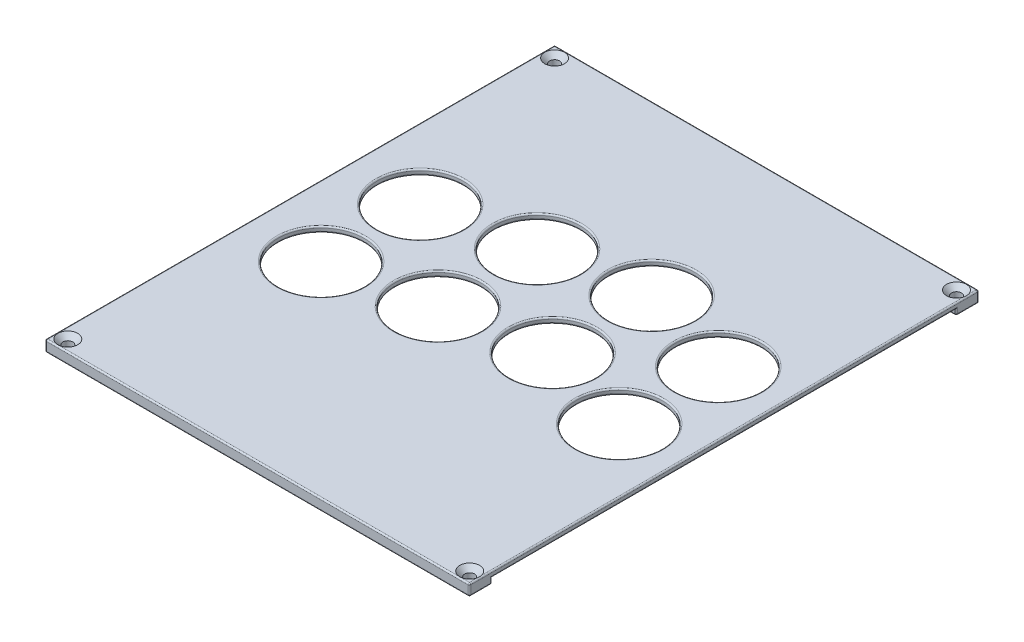
SolidWorks part; units mm, degrees
ref_plane "Front Plane" through (0, 0, 0) normal (0, 0, 1) x (1, 0, 0)
ref_plane "Top Plane" through (0, 0, 0) normal (0, 1, 0) x (1, 0, 0)
ref_plane "Right Plane" through (0, 0, 0) normal (1, 0, 0) x (0, 0, -1)
sketch "Sketch1" plane through (0, 0, 0) normal (0, 1, 0) x (1, 0, 0)
  line L0 (-125, -72.5) -> (-90.7071, -65.5) construction
  line L1 (0, 0) -> (-150, 0)
  line L2 (0, 0) -> (0, -180)
  line L3 (0, -180) -> (-150, -180)
  line L4 (-150, 0) -> (-150, -180)
  line L5 (-90.7071, -65.5) -> (-56.2253, -59.5) construction
  line L6 (-56.2253, -59.5) -> (-22.6842, -69.5) construction
  line L7 (-22.6842, -69.5) -> (-22.6842, -104.5) construction
  line L8 (-22.6842, -104.5) -> (-56.2253, -94.5) construction
  line L9 (-56.2253, -94.5) -> (-90.7071, -100.5) construction
  line L10 (-90.7071, -100.5) -> (-125, -107.5) construction
  line L11 (-125, -107.5) -> (-125, -72.5) construction
  line L12 (-90.7071, -100.5) -> (-90.7071, -65.5) construction
  line L13 (-56.2253, -94.5) -> (-56.2253, -59.5) construction
  line L14 (-22.6842, -69.5) -> (-22.6842, -59.5) construction
  line L15 (-22.6842, -59.5) -> (-56.2253, -59.5) construction
  line L16 (-56.2253, -59.5) -> (-90.7071, -59.5) construction
  line L17 (-90.7071, -65.5) -> (-90.7071, -59.5) construction
  line L18 (-90.7071, -65.5) -> (-125, -65.5) construction
  line L19 (-125, -65.5) -> (-125, -72.5) construction
  line L20 (-125, -72.5) -> (-150, -72.5) construction
  line L21 (-125, -72.5) -> (-125, 0) construction
  line L22 (-22.6842, -69.5) -> (0, -69.5) construction
  line L23 (-75, -145) -> (-150, -145) construction
  line L24 (-150, -172) -> (-142, -172) construction
  line L25 (-142, -172) -> (-142, -180) construction
  line L26 (-8, -180) -> (-8, -172) construction
  line L27 (-8, -172) -> (0, -172) construction
  line L28 (0, -8) -> (-8, -8) construction
  line L29 (-8, -8) -> (-8, 0) construction
  line L30 (-142, 0) -> (-142, -8) construction
  line L31 (-142, -8) -> (-150, -8) construction
  line L32 (-142, -8) -> (-150, 0) construction
  line L33 (-8, -8) -> (0, 0) construction
  line L34 (-8, -172) -> (0, -180) construction
  line L35 (-150, -180) -> (-142, -172) construction
  line L36 (-125, -107.5) -> (-125, -180) construction
  line L37 (-47.5, -162) -> (-102.5, -162) construction
  line L38 (-47.5, -162) -> (-47.5, -128) construction
  line L39 (-47.5, -128) -> (-102.5, -128) construction
  line L40 (-102.5, -162) -> (-102.5, -128) construction
  line L41 (-47.5, -162) -> (-102.5, -128) construction
  line L42 (-47.5, -128) -> (-102.5, -162) construction
  line L43 (-75, -145) -> (0, -145) construction
  line L44 (-75, -145) -> (-75, -180) construction
  line L45 (-142, -2) -> (-8, -2)
  line L46 (-100.1329, -128) -> (-101.3164, -125.95)
  line L47 (-101.3164, -125.95) -> (-103.6836, -125.95)
  line L48 (-103.6836, -125.95) -> (-104.8671, -128)
  line L49 (-104.8671, -128) -> (-103.6836, -130.05)
  line L50 (-103.6836, -130.05) -> (-101.3164, -130.05)
  line L51 (-101.3164, -130.05) -> (-100.1329, -128)
  line L52 (-45.1329, -128) -> (-46.3164, -125.95)
  line L53 (-46.3164, -125.95) -> (-48.6836, -125.95)
  line L54 (-48.6836, -125.95) -> (-49.8671, -128)
  line L55 (-49.8671, -128) -> (-48.6836, -130.05)
  line L56 (-48.6836, -130.05) -> (-46.3164, -130.05)
  line L57 (-46.3164, -130.05) -> (-45.1329, -128)
  line L58 (-46.3164, -164.05) -> (-45.1329, -162)
  line L59 (-45.1329, -162) -> (-46.3164, -159.95)
  line L60 (-46.3164, -159.95) -> (-48.6836, -159.95)
  line L61 (-48.6836, -159.95) -> (-49.8671, -162)
  line L62 (-49.8671, -162) -> (-48.6836, -164.05)
  line L63 (-48.6836, -164.05) -> (-46.3164, -164.05)
  line L64 (-100.1329, -162) -> (-101.3164, -159.95)
  line L65 (-101.3164, -159.95) -> (-103.6836, -159.95)
  line L66 (-103.6836, -159.95) -> (-104.8671, -162)
  line L67 (-104.8671, -162) -> (-103.6836, -164.05)
  line L68 (-103.6836, -164.05) -> (-101.3164, -164.05)
  line L69 (-101.3164, -164.05) -> (-100.1329, -162)
  line L70 (-106, -166) -> (-44, -166)
  line L71 (-106, -166) -> (-106, -124)
  line L72 (-106, -124) -> (-44, -124)
  line L73 (-44, -166) -> (-44, -124)
  line L74 (-106, -166) -> (-44, -124) construction
  line L75 (-106, -124) -> (-44, -166) construction
  line L76 (-148, -8) -> (-148, -172)
  line L77 (-142, -178) -> (-8, -178)
  line L78 (-142, -2) -> (-142, -8)
  line L79 (-142, -8) -> (-148, -8)
  line L80 (-8, -2) -> (-8, -8)
  line L81 (-8, -8) -> (0, -8)
  line L82 (0, -172) -> (-8, -172)
  line L83 (-8, -172) -> (-8, -178)
  line L84 (-142, -178) -> (-142, -172)
  line L85 (-142, -172) -> (-148, -172)
  line L86 (-145.7, -90) -> (-145.7, -80)
  line L87 (-2.3, -2.3) -> (-147.7, -2.3) construction
  line L89 (-2.3, -177.7) -> (-147.7, -177.7) construction
  line L90 (-2.3, -2.3) -> (-2.3, -177.7) construction
  line L91 (-75, -2.3) -> (-65, -2.3)
  line L92 (-65, -2.3) -> (-65, -4.3)
  line L93 (-65, -4.3) -> (-85, -4.3)
  line L94 (-85, -4.3) -> (-85, -2.3)
  line L95 (-85, -2.3) -> (-75, -2.3)
  line L96 (-145.7, -80) -> (-143.7, -80)
  line L97 (-143.7, -80) -> (-143.7, -100)
  line L98 (-143.7, -100) -> (-145.7, -100)
  line L99 (-145.7, -100) -> (-145.7, -90)
  line L100 (-75, -177.7) -> (-65, -177.7)
  line L101 (-65, -177.7) -> (-65, -175.7)
  line L102 (-65, -175.7) -> (-85, -175.7)
  line L103 (-85, -175.7) -> (-85, -177.7)
  line L104 (-85, -177.7) -> (-75, -177.7)
  line L105 (-147.7, -2.3) -> (-147.7, -177.7) construction
  line L106 (-148, -90) -> (-145.7, -90) construction
  circle A16 centre (-125, -72.5) radius 15 construction
  circle A17 centre (-90.7071, -65.5) radius 15 construction
  circle A18 centre (-56.2253, -59.5) radius 15 construction
  circle A19 centre (-22.6842, -69.5) radius 15 construction
  circle A20 centre (-125, -107.5) radius 15 construction
  circle A21 centre (-90.7071, -100.5) radius 15 construction
  circle A22 centre (-56.2253, -94.5) radius 15 construction
  circle A23 centre (-22.6842, -104.5) radius 15 construction
  circle A24 centre (-125, -72.5) radius 15.2
  circle A25 centre (-90.7071, -65.5) radius 15.2
  circle A26 centre (-56.2253, -59.5) radius 15.2
  circle A27 centre (-22.6842, -69.5) radius 15.2
  circle A28 centre (-22.6842, -104.5) radius 15.2
  circle A29 centre (-56.2253, -94.5) radius 15.2
  circle A30 centre (-90.7071, -100.5) radius 15.2
  circle A31 centre (-125, -107.5) radius 15.2
  circle A32 centre (-146, -4) radius 1.75
  circle A33 centre (-4, -4) radius 1.75
  circle A34 centre (-4, -176) radius 1.75
  circle A35 centre (-146, -176) radius 1.75
  circle A36 centre (-102.5, -128) radius 2.05 construction
  circle A37 centre (-47.5, -128) radius 2.05 construction
  circle A38 centre (-47.5, -162) radius 2.05 construction
  circle A39 centre (-102.5, -162) radius 2.05 construction
  point P23 (-75, -145)
  dimension "D1" = 30
  dimension "D7" = 3.5
  dimension "D14" = 4.1
  dimension "D22" = 2.3
  dimension "D3" = 10
  dimension "D4" = 6
  dimension "D5" = 7
  dimension "D6" = 8
  dimension "D8" = 0.2
  dimension "D2" = 35
  dimension "D9" = 180
  dimension "D10" = 150
  dimension "D11" = 55
  dimension "D12" = 34
  dimension "D13" = 35
  dimension "D15" = 42
  dimension "D16" = 62
  dimension "D17" = 2
  dimension "D18" = 2
  dimension "D19" = 2
  dimension "D20" = 25
  dimension "D21" = 2
  dimension "D23" = 2
  dimension "D24" = 20
  dimension "D25" = 20
  dimension "D26" = 2
  dimension "D27" = 20
  dimension "D28" = 2.3
extrude "Boss-Extrude1" add sketch "Sketch1" along normal blind 2 contours L1 L4 L3 L2 A35 A34 A33 A32 A31 A30 A29 A28 A27 A26 A25 A24 L73 L70 L71 L72 | L70 L73 L72 L71 L51 L50 L49 L48 L47 L46 L57 L56 L55 L54 L53 L52 L63 L62 L61 L60 L59 L58 L69 L68 L67 L66 L65 L64 | L68 L69 L64 L65 L66 L67 | L84 L85 L76 L79 L78 L45 L80 L81 L2 L1 L4 L3 L82 L83 L77 A35 A34 A33 A32 | L48 L49 L50 L51 L46 L47 | L52 L53 L54 L55 L56 L57 | L58 L59 L60 L61 L62 L63 | L102 L103 L104 L100 L101 | L97 L98 L99 L86 L96 | L93 L94 L95 L91 L92 region at (-0.2343, 0, 4) region at (-73.8907, 0, 83.6694) region at (-102.5, 0, 162) region at (-75, 0, 145)
extrude "Boss-Extrude2" add sketch "Sketch1<4>" against normal blind 2 contours L84 L85 L76 L79 L78 L45 L80 L81 L2 L1 L4 L3 L82 L83 L77 A35 A34 A33 A32 region at (-0.2343, 0, 4)
sketch "Sketch1<4>" plane through (0, 0, 0) normal (0, 1, 0) x (1, 0, 0) same geometry as "Sketch1"
extrude "Boss-Extrude3" add sketch "Sketch1<5>" against normal blind 4 contours L102 L103 L104 L100 L101 | L97 L98 L99 L86 L96 | L93 L94 L95 L91 L92
sketch "Sketch1<5>" plane through (0, 0, 0) normal (0, 1, 0) x (1, 0, 0) same geometry as "Sketch1"
sketch "Sketch2" plane through (0, 0, 0) normal (1, 0, 0) x (0, 0, -1)
  line L9 (-180, 2) -> (0, 2)
  line L13 (0, 2) -> (0, -2)
  line L14 (0, -2) -> (-8, -2) construction
  line L15 (0, -2) -> (-8, -2)
  line L16 (-8, -2) -> (-8, 0)
  line L17 (-8, 0) -> (-172, 0)
  line L18 (-172, 0) -> (-172, -2)
  line L19 (-172, -2) -> (-180, -2)
  line L22 (-180, -2) -> (-180, 2)
  line M2 (0, -2) -> (0, 2)
  line M4 (-180, 2) -> (-180, -2)
  line M9 (-172, 0) -> (-8, 0)
  line M10 (0, 2) -> (-180, 2)
  line M24 (-8, 0) -> (-8, -2)
  line M25 (-8, -2) -> (0, -2)
  line M26 (-180, -2) -> (-172, -2)
  line M27 (-172, -2) -> (-172, 0)
extrude "Cut-Extrude1" cut sketch "Sketch2" against normal blind 0.1 contours M27 M9 M24 M25 M2 M10 M4 M26 region at (0, 0.8367, 90)
fillet "Fillet1" radius 0.5 63 edges at (-150, 0, 0) (-150, 0, 180) (-75.05, 2, 0) (-0.1, 0, 0) (-150, 2, 90) (-75.05, 2, 180) (-0.1, 0, 180) (-22.6842, 0, 119.7) (-22.6842, 2, 119.7) (-22.6842, 0, 84.7) (-22.6842, 2, 84.7) (-56.2253, 0, 74.7) (-56.2253, 2, 74.7) (-56.2253, 0, 109.7) (-56.2253, 2, 109.7) (-90.7071, 0, 115.7) (-90.7071, 2, 115.7) (-90.7071, 0, 80.7) (-90.7071, 2, 80.7) (-125, 0, 87.7) (-125, 2, 87.7) (-125, 0, 122.7) (-125, 2, 122.7) (-0.1, 2, 90) (-0.1, 0, 90) (-75.05, -2, 0) (-150, -2, 90) (-75.05, -2, 180) (-0.1, -2, 176) (-0.1, -2, 4) (-0.1, -1, 8) (-0.1, -1, 172) (-8, -1, 8) (-4.05, -2, 172) (-8, -2, 175) (-75, -2, 178) (-142, -2, 175) (-145, -2, 172) (-148, -2, 90) (-145, -2, 8) (-142, -2, 5) (-75, -2, 2) (-8, -2, 5) (-4.05, -2, 8) (-146, -2, 5.75) (-4, -2, 5.75) (-4, -2, 177.75) (-146, -2, 177.75) (-142, -1, 8) (-142, -1, 172) (-8, -1, 172) (-75, -4, 175.7) (-85, -4, 176.7) (-75, -4, 177.7) (-65, -4, 176.7) (-145.7, -4, 90) (-144.7, -4, 100) (-143.7, -4, 90) (-144.7, -4, 80) (-75, -4, 2.3) (-85, -4, 3.3) (-75, -4, 4.3) (-65, -4, 3.3)
chamfer "Chamfer1" distance 1.75 angle 45 4 edges at (-146, 2, 177.75) (-4, 2, 177.75) (-4, 2, 5.75) (-146, 2, 5.75)
